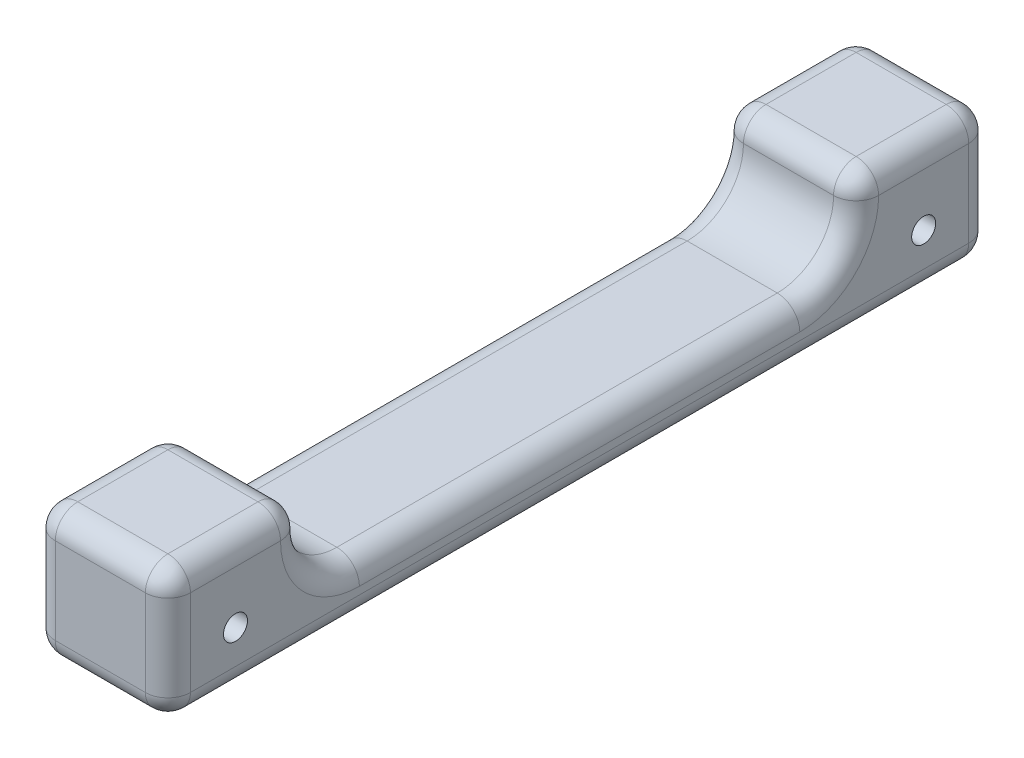
SolidWorks part; units mm, degrees
ref_plane "前视基准面" through (0, 0, 0) normal (0, 0, 1) x (1, 0, 0)
ref_plane "上视基准面" through (0, 0, 0) normal (0, 1, 0) x (1, 0, 0)
ref_plane "右视基准面" through (0, 0, 0) normal (1, 0, 0) x (0, 0, -1)
other "Configuration Table"
sketch "草图1" plane through (0, 0, 0) normal (0, 1, 0) x (1, 0, 0)
  line L1 (-6.2, 6.2) -> (6.2, 6.2)
  line L2 (-6.2, 6.2) -> (-6.2, -6.2)
  line L3 (-6.2, -6.2) -> (6.2, -6.2)
  line L4 (6.2, 6.2) -> (6.2, -6.2)
  line L5 (-6.2, 6.2) -> (6.2, -6.2) construction
  line L6 (-6.2, -6.2) -> (6.2, 6.2) construction
  point P0 (0, 0)
  dimension "D1" = 12.4
  dimension "D2" = 12.4
extrude "拉伸-薄壁1" add sketch "草图1" along normal blind 15 thin thin type one direction wall 2.8
sketch "草图2" plane through (0, 15, 0) normal (0, 1, 0) x (1, 0, 0)
  line L1 (-9, 9) -> (9, 9)
  line L2 (-9, 9) -> (-9, -9)
  line L3 (-9, -9) -> (9, -9)
  line L4 (9, 9) -> (9, -9)
extrude "凸台-拉伸1" add sketch "草图2" along normal blind 2.5
fillet "圆角1" radius 3 4 edges at (0, 17.5, -9) (9, 17.5, 0) (0, 17.5, 9) (-9, 17.5, 0)
sketch "草图3" plane through (0, 0, 9) normal (0, 0, 1) x (1, 0, 0)
  line L0 (9, 14.5) -> (9, 0) construction
  line L1 (-9, 0) -> (9, 0)
  line L2 (-9, 0) -> (-9, 7)
  line L3 (-9, 7) -> (9, 7)
  line L4 (9, 0) -> (9, 7)
  dimension "D1" = 7
extrude "凸台-拉伸2" add sketch "草图3" along normal blind 36.83
fillet "圆角2" radius 7.5 1 edges at (0, 7, 9)
fillet "圆角3" radius 3 4 edges at (-9, 7.25, -9) (9, 7.25, -9) (8.1213, 16.6213, -8.1213) (-8.1213, 16.6213, -8.1213)
sketch "草图6" plane through (-6.2, 0, 0) normal (1, 0, 0) x (0, 0, -1)
  line L0 (0, 0) -> (0, 15) construction
  line L1 (6.2, 0) -> (-6.2, 0) construction
  line L2 (6.2, 15) -> (-6.2, 15) construction
  circle A0 centre (0, 7.5) radius 1.6
  dimension "D1" = 3.2
extrude "切除-拉伸1" cut sketch "草图6" against normal blind 37 and the other way blind 37
mirror "镜向1" about plane through (0, 0, 45.83) normal (0, 0, -1) of bodies 110 108
fillet "圆角4" radius 3 12 edges at (8.1213, 16.6213, 83.5387) (9, 9.1967, 80.4633) (-9, 9.1967, 80.4633) (8.1213, 16.6213, 8.1213) (9, 9.1967, 11.1967) (-8.1213, 16.6213, 83.5387) (-8.1213, 16.6213, 8.1213) (-9, 9.1967, 11.1967) (9, 0, 45.83) (-9, 0, 45.83) (9, 7, 45.83) (-9, 7, 45.83)
